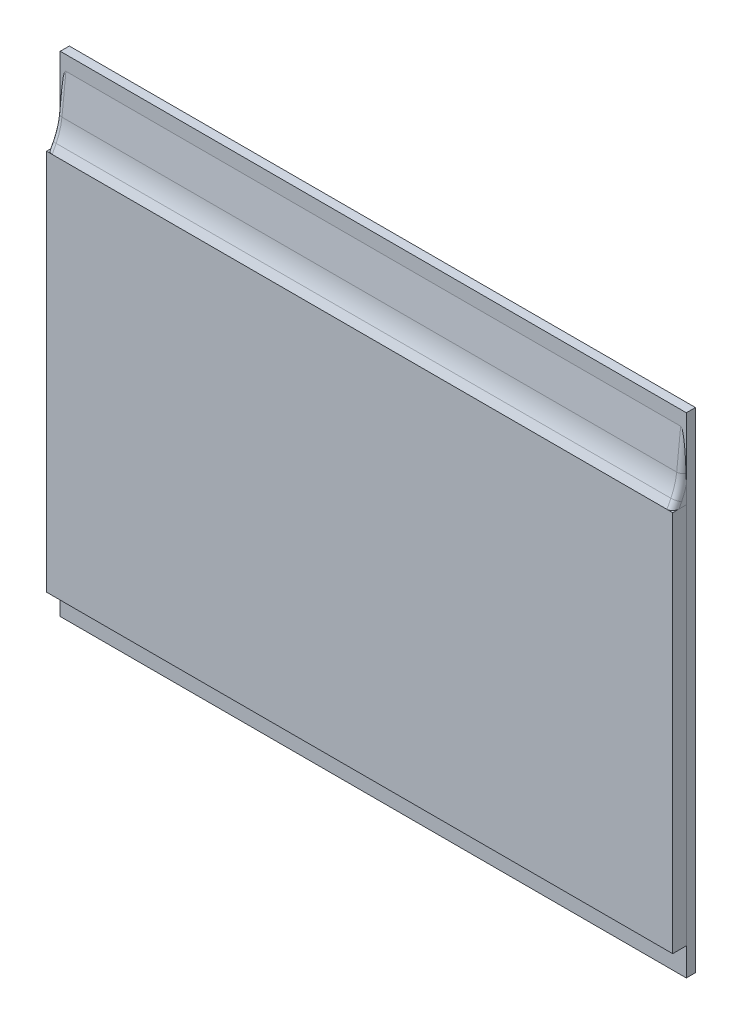
SolidWorks part; units mm, degrees
ref_plane "Front Plane" through (0, 0, 0) normal (0, 0, 1) x (1, 0, 0)
ref_plane "Top Plane" through (0, 0, 0) normal (0, 1, 0) x (1, 0, 0)
ref_plane "Right Plane" through (0, 0, 0) normal (1, 0, 0) x (0, 0, -1)
sketch "Sketch1" plane through (0, 0, 0) normal (0, 0, 1) x (1, 0, 0)
  line L1 (-27.5, 21.5) -> (27.5, 21.5)
  line L2 (-27.5, 21.5) -> (-27.5, -21.5)
  line L3 (-27.5, -21.5) -> (27.5, -21.5)
  line L4 (27.5, 21.5) -> (27.5, -21.5)
  line L5 (-27.5, 21.5) -> (27.5, -21.5) construction
  line L6 (-27.5, -21.5) -> (27.5, 21.5) construction
  point P0 (0, 0)
  dimension "D1" = 55
  dimension "D2" = 43
extrude "GlassBase" add sketch "Sketch1" along normal blind 0.8
sketch "Sketch3" plane through (0, 0, 0.8) normal (0, 0, 1) x (1, 0, 0)
  line L0 (0, 21.5) -> (0, -21.5) construction
  line L1 (-23.995, -16.215) -> (23.995, -16.215)
  line L2 (-23.995, -16.215) -> (-23.995, 11.615)
  line L3 (-23.995, 11.615) -> (23.995, 11.615)
  line L4 (23.995, -16.215) -> (23.995, 11.615)
  line L5 (-23.995, -16.215) -> (23.995, 11.615) construction
  line L6 (-23.995, 11.615) -> (23.995, -16.215) construction
  line L7 (27.5, 21.5) -> (-27.5, 21.5) construction
  line L8 (-27.5, -21.5) -> (27.5, -21.5) construction
  line L9 (-23.995, -2.3) -> (23.995, -2.3) construction
  line L11 (-25.5, 13.2) -> (25.5, 13.2)
  line L12 (-25.5, 13.2) -> (-25.5, -17.8)
  line L13 (-25.5, -17.8) -> (25.5, -17.8)
  line L14 (25.5, 13.2) -> (25.5, -17.8)
  line L15 (-25.5, 13.2) -> (25.5, -17.8) construction
  line L16 (-25.5, -17.8) -> (25.5, 13.2) construction
  point P0 (0, -2.3)
  point P13 (0, -2.3)
  dimension "D1" = 47.99
  dimension "D2" = 27.83
  dimension "D3" = 23.8
  dimension "D4" = 51
  dimension "D5" = 31
extrude "Boss-Extrude3" add sketch "Sketch3" along normal blind 0.05 separate body
sketch "Sketch4" plane through (0, 0, 0.8) normal (0, 0, 1) x (1, 0, 0)
  line L0 (-23.995, 11.615) -> (-23.995, -16.215) construction
  line L1 (23.995, 11.615) -> (-23.995, 11.615) construction
  line L2 (-23.995, -16.215) -> (23.995, -16.215) construction
  line L3 (23.995, -16.215) -> (23.995, 11.615) construction
  line L4 (-23.995, 11.615) -> (-23.995, -16.215)
  line L5 (23.995, 11.615) -> (-23.995, 11.615)
  line L6 (-23.995, -16.215) -> (23.995, -16.215)
  line L7 (23.995, -16.215) -> (23.995, 11.615)
extrude "Boss-Extrude4" add sketch "Sketch4" along normal blind 0.05 separate body
sketch "Sketch5" plane through (0, 0, 0.85) normal (0, 0, 1) x (1, 0, 0)
  line L14 (25.5, 13.2) -> (-25.5, 13.2) construction
  line L15 (-25.5, 13.2) -> (-25.5, -17.8) construction
  line L16 (25.5, -17.8) -> (25.5, 13.2) construction
  line L17 (-25.5, -17.8) -> (25.5, -17.8) construction
  line L18 (-24.5, -17.3) -> (24.5, -17.3)
  line L19 (25, -16.8) -> (25, 12.2)
  line L20 (-25, 12.2) -> (-25, -16.8)
  line L21 (24.5, 12.7) -> (-24.5, 12.7)
  line L22 (25.5, 13.2) -> (-25.5, 13.2)
  line L23 (-25.5, 13.2) -> (-25.5, -17.8)
  line L24 (25.5, -17.8) -> (25.5, 13.2)
  line L25 (-25.5, -17.8) -> (25.5, -17.8)
  arc A0 (-24.5, -17.3) -> (-25, -16.8) centre (-24.5, -16.8) cw
  arc A1 (24.5, -17.3) -> (25, -16.8) centre (24.5, -16.8) ccw
  arc A2 (25, 12.2) -> (24.5, 12.7) centre (24.5, 12.2) ccw
  arc A3 (-25, 12.2) -> (-24.5, 12.7) centre (-24.5, 12.2) cw
  dimension "D2" = 0.5
  dimension "D1" = 51
  dimension "D3" = 31
extrude "Boss-Extrude5" add sketch "Sketch5" along normal blind 0.05 separate body
sketch "Sketch6" plane through (0, 0, 0.8) normal (0, 0, 1) x (1, 0, 0)
  line L0 (-27.5, 21.5) -> (-27.5, -21.5) construction
  line L1 (-27.5, 14.5) -> (27.5, 14.5)
  line L2 (-27.5, 14.5) -> (-27.5, -19.05)
  line L3 (-27.5, -19.05) -> (27.5, -19.05)
  line L4 (27.5, 14.5) -> (27.5, -19.05)
  line L5 (27.5, -21.5) -> (27.5, 21.5) construction
  line L6 (27.5, 21.5) -> (-27.5, 21.5) construction
  line L7 (-27.5, -21.5) -> (27.5, -21.5) construction
  dimension "D1" = 7
  dimension "D2" = 2.45
extrude "Boss-Extrude6" add sketch "Sketch6" along normal blind 1.2 separate body
ref_plane "Plane2" through (-27.5, 14.5, 0.8) normal (-1, 0, 0) x (0, 0, 1)
sketch "Sketch8" plane through (-27.5, 14.5, 0.8) normal (-1, 0, 0) x (0, 0, 1)
  line L0 (1.2, 0) -> (0.8586, 0.6749)
  line L1 (0, 7) -> (0, -36) construction
  line L2 (0, 5.7265) -> (0.3474, 2.4109)
  line L4 (0, 5.7265) -> (0, 0)
  line L5 (0, 0) -> (1.2, 0)
  arc A0 (0.8586, 0.6749) -> (0.3474, 2.4109) centre (5.3202, 2.9319) cw
  dimension "D1" = 5
extrude "Boss-Extrude7" add sketch "Sketch8" against normal blind 55 separate body
fillet "Fillet1" radius 0.5 3 edges at (-27.5, 14.8375, 1.8293) (-27.5, 18.5687, 0.9737) (-27.5, 16.0196, 1.3238)
fillet "Fillet2" radius 0.5 3 edges at (27.5, 14.8375, 1.8293) (27.5, 18.5687, 0.9737) (27.5, 16.0196, 1.3238)
